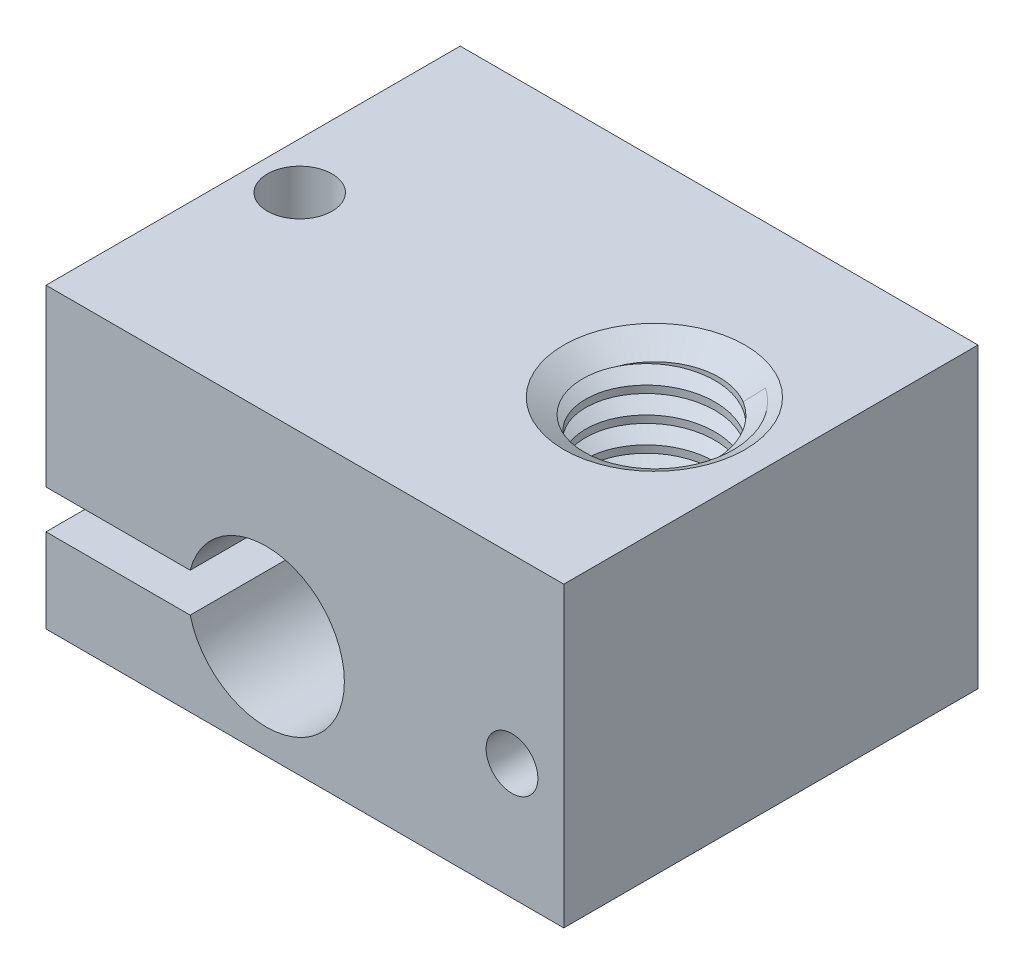
SolidWorks part; units mm, degrees
material "Copper"
ref_plane "Front Plane" through (0, 0, 0) normal (0, 0, 1) x (1, 0, 0)
ref_plane "Top Plane" through (0, 0, 0) normal (0, 1, 0) x (1, 0, 0)
ref_plane "Right Plane" through (0, 0, 0) normal (1, 0, 0) x (0, 0, -1)
sketch "Sketch1" plane through (0, 0, 0) normal (0, 1, 0) x (1, 0, 0)
  line L1 (10, 8) -> (-10, 8)
  line L2 (10, 8) -> (10, -8)
  line L3 (10, -8) -> (-10, -8)
  line L4 (-10, 8) -> (-10, -8)
  line L5 (10, 8) -> (-10, -8) construction
  line L6 (10, -8) -> (-10, 8) construction
  point P0 (0, 0)
  dimension "D1" = 20
  dimension "D2" = 16
extrude "Boss-Extrude1" add sketch "Sketch1" along normal mid plane 11.5
sketch "Sketch2" plane through (0, 5.75, 0) normal (0, 1, 0) x (1, 0, 0)
  line L0 (0, 8) -> (0, -8) construction
  line L1 (10, 8) -> (-10, 8) construction
  line L2 (-10, -8) -> (10, -8) construction
  line L3 (-10, 0) -> (10, 0) construction
  line L4 (-10, 8) -> (-10, -8) construction
  line L5 (10, -8) -> (10, 8) construction
  circle A0 centre (5.5, 0) radius 2.5
  circle A1 centre (-8.2, 0) radius 1.25
  dimension "D1" = 5
  dimension "D4" = 2.5
  dimension "D2" = 4.5
  dimension "D3" = 1.8
extrude "Cut-Extrude1" cut sketch "Sketch2" against normal up to next
sketch "Sketch3" plane through (0, 0, 8) normal (0, 0, 1) x (1, 0, 0)
  line L0 (0, 0) -> (-18.9264, 0) construction
  line L1 (-18.9264, 0) -> (-18.9264, -4.2761) construction
  line L2 (-18.9264, -4.2761) -> (0, -4.2761) construction
  line L3 (0, -4.2761) -> (0, 0) construction
  line L4 (0, -1.75) -> (-17.234, -1.75) construction
  line L5 (-10, -5.75) -> (10, -5.75) construction
  line L6 (-15.1475, -1.75) -> (-15.1475, -1)
  line L7 (-15.1475, -1) -> (-4.4306, -1)
  line L9 (-15.1475, -1.75) -> (-15.1475, -2.5)
  line L10 (-15.1475, -2.5) -> (-4.4306, -2.5)
  line L11 (10, 5.75) -> (10, -5.75) construction
  arc A0 (-4.4306, -1) -> (-4.4306, -2.5) centre (-1.5, -1.75) cw
  dimension "D2" = 3.025
  dimension "D1" = 4
  dimension "D3" = 11.5
  dimension "D4" = 0.75
  dimension "D5" = 0.75
extrude "Cut-Extrude2" cut sketch "Sketch3" against normal up to next
sketch "Sketch4" plane through (0, 0, 8) normal (0, 0, 1) x (1, 0, 0)
  line L0 (-10, -5.75) -> (10, -5.75) construction
  line L7 (10, 5.75) -> (10, -5.75) construction
  circle A0 centre (8, -1.25) radius 1
  dimension "D5" = 2
  dimension "D1" = 4.5
  dimension "D2" = 2
extrude "Cut-Extrude3" cut sketch "Sketch4" against normal through all
ref_plane "Plane1" through (0, 8.75, 0) normal (0, 1, 0) x (1, 0, 0)
sketch "Sketch6" plane through (0, 8.75, 0) normal (0, 1, 0) x (1, 0, 0)
  circle A0 centre (5.5, 0) radius 2.5 construction
  circle A1 centre (5.5, 0) radius 2.5 construction
  circle A2 centre (5.5, 0) radius 3.125
  dimension "D1" = 6.25
curve "Helix/Spiral1" pitch 1 height 20 radius 3.125 centre (5.5, 8.75, 0) axis (0, -1, 0) start towards (0, 0, 1)
chamfer "Chamfer1" distance 1 angle 30 1 edges at (5.5, 5.75, 2.5) first distance on face at (-8.2, 5.75, 1.25)
sketch "Sketch7" plane through (0, 0, 0) normal (0, 0, 1) x (1, 0, 0)
  line L0 (8.6229, 6.3692) -> (6.1425, 6.3692) construction
  line L1 (8.6229, 6.3692) -> (7.7482, 6.8742)
  line L2 (7.7482, 6.8742) -> (7.7482, 5.8642)
  line L3 (8.6229, 6.3692) -> (7.7482, 5.8642)
  spline S0 degree 3 poles (3.2903, 8.75) (3.5777, 8.7293) (4.2738, 8.6874) (5.4998, 8.625) (6.7271, 8.5625) (7.7672, 8.5) (8.4623, 8.4375) (8.7064, 8.375) (8.4623, 8.3125) (7.7672, 8.25) (6.727, 8.1875) (5.5, 8.125) (4.273, 8.0625) (3.2328, 8) (2.5377, 7.9375) (2.2936, 7.875) (2.5377, 7.8125) (3.2328, 7.75) (4.273, 7.6875) (5.5, 7.625) (6.727, 7.5625) (7.7672, 7.5) (8.4623, 7.4375) (8.7064, 7.375) (8.4623, 7.3125) (7.7672, 7.25) (6.727, 7.1875) (5.5, 7.125) (4.273, 7.0625) (3.2328, 7) (2.5377, 6.9375) (2.2936, 6.875) (2.5377, 6.8125) (3.2328, 6.75) (4.273, 6.6875) (5.5, 6.625) (6.727, 6.5625) (7.7672, 6.5) (8.4623, 6.4375) (8.7064, 6.375) (8.4623, 6.3125) (7.7672, 6.25) (6.727, 6.1875) (5.5, 6.125) (4.273, 6.0625) (3.2328, 6) (2.5377, 5.9375) (2.2936, 5.875) (2.5377, 5.8125) (3.2328, 5.75) (4.273, 5.6875) (5.5, 5.625) (6.727, 5.5625) (7.7672, 5.5) (8.4623, 5.4375) (8.7064, 5.375) (8.4623, 5.3125) (7.7672, 5.25) (6.727, 5.1875) (5.5, 5.125) (4.273, 5.0625) (3.2328, 5) (2.5377, 4.9375) (2.2936, 4.875) (2.5377, 4.8125) (3.2328, 4.75) (4.273, 4.6875) (5.5, 4.625) (6.727, 4.5625) (7.7672, 4.5) (8.4623, 4.4375) (8.7064, 4.375) (8.4623, 4.3125) (7.7672, 4.25) (6.727, 4.1875) (5.5, 4.125) (4.273, 4.0625) (3.2328, 4) (2.5377, 3.9375) (2.2936, 3.875) (2.5377, 3.8125) (3.2328, 3.75) (4.273, 3.6875) (5.5, 3.625) (6.727, 3.5625) (7.7672, 3.5) (8.4623, 3.4375) (8.7064, 3.375) (8.4623, 3.3125) (7.7672, 3.25) (6.727, 3.1875) (5.5, 3.125) (4.273, 3.0625) (3.2328, 3) (2.5377, 2.9375) (2.2936, 2.875) (2.5377, 2.8125) (3.2328, 2.75) (4.273, 2.6875) (5.5, 2.625) (6.727, 2.5625) (7.7672, 2.5) (8.4623, 2.4375) (8.7064, 2.375) (8.4623, 2.3125) (7.7672, 2.25) (6.727, 2.1875) (5.5, 2.125) (4.273, 2.0625) (3.2328, 2) (2.5377, 1.9375) (2.2936, 1.875) (2.5377, 1.8125) (3.2328, 1.75) (4.273, 1.6875) (5.5, 1.625) (6.727, 1.5625) (7.7672, 1.5) (8.4623, 1.4375) (8.7064, 1.375) (8.4623, 1.3125) (7.7672, 1.25) (6.727, 1.1875) (5.5, 1.125) (4.273, 1.0625) (3.2328, 1) (2.5377, 0.9375) (2.2936, 0.875) (2.5377, 0.8125) (3.2328, 0.75) (4.273, 0.6875) (5.5, 0.625) (6.727, 0.5625) (7.7672, 0.5) (8.4623, 0.4375) (8.7064, 0.375) (8.4623, 0.3125) (7.7672, 0.25) (6.727, 0.1875) (5.5, 0.125) (4.273, 0.0625) (3.2328, 0) (2.5377, -0.0625) (2.2936, -0.125) (2.5377, -0.1875) (3.2328, -0.25) (4.273, -0.3125) (5.5, -0.375) (6.727, -0.4375) (7.7672, -0.5) (8.4623, -0.5625) (8.7064, -0.625) (8.4623, -0.6875) (7.7672, -0.75) (6.727, -0.8125) (5.5, -0.875) (4.273, -0.9375) (3.2328, -1) (2.5377, -1.0625) (2.2936, -1.125) (2.5377, -1.1875) (3.2328, -1.25) (4.273, -1.3125) (5.5, -1.375) (6.727, -1.4375) (7.7672, -1.5) (8.4623, -1.5625) (8.7064, -1.625) (8.4623, -1.6875) (7.7672, -1.75) (6.727, -1.8125) (5.5, -1.875) (4.273, -1.9375) (3.2328, -2) (2.5377, -2.0625) (2.2936, -2.125) (2.5377, -2.1875) (3.2328, -2.25) (4.273, -2.3125) (5.5, -2.375) (6.727, -2.4375) (7.7672, -2.5) (8.4623, -2.5625) (8.7064, -2.625) (8.4623, -2.6875) (7.7672, -2.75) (6.727, -2.8125) (5.5, -2.875) (4.273, -2.9375) (3.2328, -3) (2.5377, -3.0625) (2.2936, -3.125) (2.5377, -3.1875) (3.2328, -3.25) (4.273, -3.3125) (5.5, -3.375) (6.727, -3.4375) (7.7672, -3.5) (8.4623, -3.5625) (8.7064, -3.625) (8.4623, -3.6875) (7.7672, -3.75) (6.727, -3.8125) (5.5, -3.875) (4.273, -3.9375) (3.2328, -4) (2.5377, -4.0625) (2.2936, -4.125) (2.5377, -4.1875) (3.2328, -4.25) (4.273, -4.3125) (5.5, -4.375) (6.727, -4.4375) (7.7672, -4.5) (8.4623, -4.5625) (8.7064, -4.625) (8.4623, -4.6875) (7.7672, -4.75) (6.727, -4.8125) (5.5, -4.875) (4.273, -4.9375) (3.2328, -5) (2.5377, -5.0625) (2.2936, -5.125) (2.5377, -5.1875) (3.2328, -5.25) (4.273, -5.3125) (5.5, -5.375) (6.727, -5.4375) (7.7672, -5.5) (8.4623, -5.5625) (8.7064, -5.625) (8.4623, -5.6875) (7.7672, -5.75) (6.727, -5.8125) (5.5, -5.875) (4.273, -5.9375) (3.2328, -6) (2.5377, -6.0625) (2.2936, -6.125) (2.5377, -6.1875) (3.2328, -6.25) (4.273, -6.3125) (5.5, -6.375) (6.727, -6.4375) (7.7672, -6.5) (8.4623, -6.5625) (8.7064, -6.625) (8.4623, -6.6875) (7.7672, -6.75) (6.727, -6.8125) (5.5, -6.875) (4.273, -6.9375) (3.2328, -7) (2.5377, -7.0625) (2.2936, -7.125) (2.5377, -7.1875) (3.2328, -7.25) (4.273, -7.3125) (5.5, -7.375) (6.727, -7.4375) (7.7672, -7.5) (8.4623, -7.5625) (8.7064, -7.625) (8.4623, -7.6875) (7.7672, -7.75) (6.727, -7.8125) (5.5, -7.875) (4.273, -7.9375) (3.2328, -8) (2.5377, -8.0625) (2.2936, -8.125) (2.5377, -8.1875) (3.2328, -8.25) (4.273, -8.3125) (5.5, -8.375) (6.727, -8.4375) (7.7672, -8.5) (8.4623, -8.5625) (8.7064, -8.625) (8.4623, -8.6875) (7.7672, -8.75) (6.727, -8.8125) (5.5, -8.875) (4.273, -8.9375) (3.2328, -9) (2.5377, -9.0625) (2.2936, -9.125) (2.5377, -9.1875) (3.2328, -9.25) (4.273, -9.3125) (5.5, -9.375) (6.727, -9.4375) (7.7672, -9.5) (8.4623, -9.5625) (8.7064, -9.625) (8.4623, -9.6875) (7.7672, -9.75) (6.727, -9.8125) (5.5, -9.875) (4.273, -9.9375) (3.2328, -10) (2.5377, -10.0625) (2.2936, -10.125) (2.5377, -10.1875) (3.2328, -10.25) (4.273, -10.3125) (5.5, -10.375) (6.727, -10.4375) (7.7672, -10.5) (8.4623, -10.5625) (8.7064, -10.625) (8.4623, -10.6875) (7.7672, -10.75) (6.727, -10.8125) (5.5, -10.875) (4.273, -10.9375) (3.2328, -11) (2.5377, -11.0625) (2.2939, -11.125) (2.5369, -11.1874) (3.0029, -11.2293) (3.2903, -11.25) knots 0 0 0 0 0.003125 0.00625 0.009375 0.0125 0.015625 0.01875 0.021875 0.025 0.028125 0.03125 0.034375 0.0375 0.040625 0.04375 0.046875 0.05 0.053125 0.05625 0.059375 0.0625 0.065625 0.06875 0.071875 0.075 0.078125 0.08125 0.084375 0.0875 0.090625 0.09375 0.096875 0.1 0.103125 0.10625 0.109375 0.1125 0.115625 0.11875 0.121875 0.125 0.128125 0.13125 0.134375 0.1375 0.140625 0.14375 0.146875 0.15 0.153125 0.15625 0.159375 0.1625 0.165625 0.16875 0.171875 0.175 0.178125 0.18125 0.184375 0.1875 0.190625 0.19375 0.196875 0.2 0.203125 0.20625 0.209375 0.2125 0.215625 0.21875 0.221875 0.225 0.228125 0.23125 0.234375 0.2375 0.240625 0.24375 0.246875 0.25 0.253125 0.25625 0.259375 0.2625 0.265625 0.26875 0.271875 0.275 0.278125 0.28125 0.284375 0.2875 0.290625 0.29375 0.296875 0.3 0.303125 0.30625 0.309375 0.3125 0.315625 0.31875 0.321875 0.325 0.328125 0.33125 0.334375 0.3375 0.340625 0.34375 0.346875 0.35 0.353125 0.35625 0.359375 0.3625 0.365625 0.36875 0.371875 0.375 0.378125 0.38125 0.384375 0.3875 0.390625 0.39375 0.396875 0.4 0.403125 0.40625 0.409375 0.4125 0.415625 0.41875 0.421875 0.425 0.428125 0.43125 0.434375 0.4375 0.440625 0.44375 0.446875 0.45 0.453125 0.45625 0.459375 0.4625 0.465625 0.46875 0.471875 0.475 0.478125 0.48125 0.484375 0.4875 0.490625 0.49375 0.496875 0.5 0.503125 0.50625 0.509375 0.5125 0.515625 0.51875 0.521875 0.525 0.528125 0.53125 0.534375 0.5375 0.540625 0.54375 0.546875 0.55 0.553125 0.55625 0.559375 0.5625 0.565625 0.56875 0.571875 0.575 0.578125 0.58125 0.584375 0.5875 0.590625 0.59375 0.596875 0.6 0.603125 0.60625 0.609375 0.6125 0.615625 0.61875 0.621875 0.625 0.628125 0.63125 0.634375 0.6375 0.640625 0.64375 0.646875 0.65 0.653125 0.65625 0.659375 0.6625 0.665625 0.66875 0.671875 0.675 0.678125 0.68125 0.684375 0.6875 0.690625 0.69375 0.696875 0.7 0.703125 0.70625 0.709375 0.7125 0.715625 0.71875 0.721875 0.725 0.728125 0.73125 0.734375 0.7375 0.740625 0.74375 0.746875 0.75 0.753125 0.75625 0.759375 0.7625 0.765625 0.76875 0.771875 0.775 0.778125 0.78125 0.784375 0.7875 0.790625 0.79375 0.796875 0.8 0.803125 0.80625 0.809375 0.8125 0.815625 0.81875 0.821875 0.825 0.828125 0.83125 0.834375 0.8375 0.840625 0.84375 0.846875 0.85 0.853125 0.85625 0.859375 0.8625 0.865625 0.86875 0.871875 0.875 0.878125 0.88125 0.884375 0.8875 0.890625 0.89375 0.896875 0.9 0.903125 0.90625 0.909375 0.9125 0.915625 0.91875 0.921875 0.925 0.928125 0.93125 0.934375 0.9375 0.940625 0.94375 0.946875 0.95 0.953125 0.95625 0.959375 0.9625 0.965625 0.96875 0.971875 0.975 0.978125 0.98125 0.984375 0.9875 0.990625 0.99375 0.996875 1 1 1 1 construction
  point P7 (7.7482, 6.3692)
  dimension "D1" = 30
  dimension "D2" = 0.505
sweep "Cut-Sweep1" cut profiles "Sketch7" path "Helix/Spiral1" align with end faces yes
